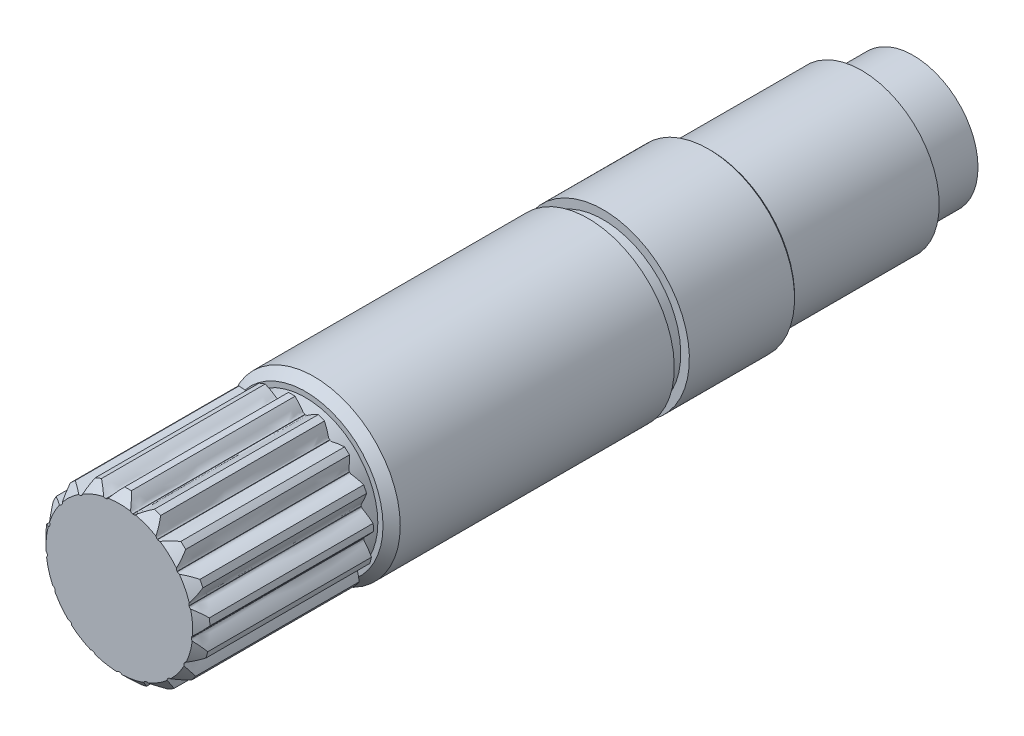
SolidWorks part; units mm, degrees
material "Alloy Steel"
ref_plane "Front Plane" through (0, 0, 0) normal (0, 0, 1) x (1, 0, 0)
ref_plane "Top Plane" through (0, 0, 0) normal (0, 1, 0) x (1, 0, 0)
ref_plane "Right Plane" through (0, 0, 0) normal (1, 0, 0) x (0, 0, -1)
sketch "Sketch12" plane through (0, 0, 0) normal (0, 0, 1) x (1, 0, 0)
  circle A0 centre (0, 0) radius 10
  dimension "D1" = 20
extrude "Shaft" add sketch "Sketch12" along normal mid plane 43
sketch "Sketch13" plane through (0, 0, 21.5) normal (0, 0, 1) x (1, 0, 0)
  circle A0 centre (0, 0) radius 8.3981
  dimension "D1" = 16.7963
extrude "Motor side relief" add sketch "Sketch13" along normal blind 1.587
sketch "Sketch14" plane through (0, 0, -21.5) normal (0, 0, -1) x (-1, 0, 0)
  circle A0 centre (0, 0) radius 8.3981
  dimension "D1" = 16.7963
sketch "Sketch15" plane through (0, 0, 23.087) normal (0, 0, 1) x (1, 0, 0)
  line L38 (4.4402, 7.1283) -> (4.4211, 7.1402)
  line L39 (4.4211, 7.1402) -> (4.4019, 7.1521)
  line L40 (1.5653, 8.251) -> (1.5432, 8.2552)
  line L41 (1.5432, 8.2552) -> (1.521, 8.2593)
  line L42 (-1.521, 8.2593) -> (-1.5432, 8.2552)
  line L43 (-1.5432, 8.2552) -> (-1.5653, 8.251)
  line L44 (-4.4019, 7.1521) -> (-4.4211, 7.1402)
  line L45 (-4.4211, 7.1402) -> (-4.4402, 7.1283)
  line L46 (-6.6882, 5.079) -> (-6.7019, 5.061)
  line L47 (-6.7019, 5.061) -> (-6.7154, 5.043)
  line L48 (-8.0713, 2.32) -> (-8.0776, 2.2983)
  line L49 (-8.0776, 2.2983) -> (-8.0837, 2.2766)
  line L50 (-8.3644, -0.7524) -> (-8.3623, -0.7749)
  line L51 (-8.3623, -0.7749) -> (-8.3602, -0.7973)
  line L52 (-7.5277, -3.7232) -> (-7.5177, -3.7434)
  line L53 (-7.5177, -3.7434) -> (-7.5076, -3.7636)
  line L54 (-5.6744, -6.1911) -> (-5.6578, -6.2063)
  line L55 (-5.6578, -6.2063) -> (-5.6411, -6.2215)
  line L56 (-3.0548, -7.8229) -> (-3.0338, -7.831)
  line L57 (-3.0338, -7.831) -> (-3.0127, -7.8392)
  line L58 (-0.0226, -8.3981) -> (0, -8.3981)
  line L59 (0, -8.3981) -> (0.0226, -8.3981)
  line L60 (3.0127, -7.8392) -> (3.0338, -7.831)
  line L61 (3.0338, -7.831) -> (3.0548, -7.8229)
  line L62 (5.6411, -6.2215) -> (5.6578, -6.2063)
  line L63 (5.6578, -6.2063) -> (5.6744, -6.1911)
  line L64 (7.5076, -3.7636) -> (7.5177, -3.7434)
  line L65 (7.5177, -3.7434) -> (7.5277, -3.7232)
  line L66 (8.3602, -0.7973) -> (8.3623, -0.7749)
  line L67 (8.3623, -0.7749) -> (8.3644, -0.7524)
  line L68 (8.0837, 2.2766) -> (8.0776, 2.2983)
  line L69 (8.0776, 2.2983) -> (8.0713, 2.32)
  line L70 (6.7154, 5.043) -> (6.7019, 5.061)
  line L71 (6.7019, 5.061) -> (6.6882, 5.079)
  arc A19 (6.6912, 6.7683) -> (6.1221, 7.2872) centre (0, 0) ccw
  arc A20 (3.7944, 8.7284) -> (3.0762, 9.0066) centre (0, 0) ccw
  arc A21 (0.3851, 9.5097) -> (-0.3851, 9.5097) centre (0, 0) ccw
  arc A22 (-3.0762, 9.0066) -> (-3.7944, 8.7284) centre (0, 0) ccw
  arc A23 (-6.1221, 7.2872) -> (-6.6912, 6.7683) centre (0, 0) ccw
  arc A24 (-8.3411, 4.5835) -> (-8.6844, 3.8941) centre (0, 0) ccw
  arc A25 (-9.4336, 1.2609) -> (-9.5047, 0.494) centre (0, 0) ccw
  arc A26 (-9.2521, -2.2321) -> (-9.0413, -2.9728) centre (0, 0) ccw
  arc A27 (-7.821, -5.4236) -> (-7.3569, -6.0382) centre (0, 0) ccw
  arc A28 (-5.3336, -7.8826) -> (-4.6788, -8.288) centre (0, 0) ccw
  arc A29 (-2.1259, -9.277) -> (-1.3689, -9.4185) centre (0, 0) ccw
  arc A30 (1.3689, -9.4185) -> (2.1259, -9.277) centre (0, 0) ccw
  arc A31 (4.6788, -8.288) -> (5.3336, -7.8826) centre (0, 0) ccw
  arc A32 (7.3569, -6.0382) -> (7.821, -5.4236) centre (0, 0) ccw
  arc A33 (9.0413, -2.9728) -> (9.2521, -2.2321) centre (0, 0) ccw
  arc A34 (9.5047, 0.494) -> (9.4336, 1.2609) centre (0, 0) ccw
  arc A35 (8.6844, 3.8941) -> (8.3411, 4.5835) centre (0, 0) ccw
  spline S0 degree 3 poles (6.6882, 5.079) (6.6486, 5.1312) (6.6257, 5.1903) (6.6128, 5.3124) (6.6277, 5.3769) (6.657, 5.5736) (6.6884, 5.8472) (6.7084, 6.2901) (6.7009, 6.6058) (6.6912, 6.7683) knots 0 0 0 0 0.125 0.125 0.25 0.25 0.5 0.75 1 1 1 1 weights 1 1 1 1 1 1 1 1 1 1
  spline S1 degree 3 poles (6.1221, 7.2872) (5.9593, 7.2818) (5.6443, 7.2602) (5.2052, 7.1994) (4.9356, 7.1428) (4.7425, 7.0956) (4.6796, 7.0748) (4.5569, 7.0763) (4.4958, 7.0937) (4.4402, 7.1283) knots 0 0 0 0 0.25 0.5 0.75 0.75 0.875 0.875 1 1 1 1 weights 1 1 1 1 1 1 1 1 1 1
  spline S2 degree 3 poles (4.4019, 7.1521) (4.3461, 7.1864) (4.3033, 7.2333) (4.2472, 7.3425) (4.2378, 7.4081) (4.194, 7.602) (4.1245, 7.8685) (3.9832, 8.2887) (3.8621, 8.5804) (3.7944, 8.7284) knots 0 0 0 0 0.125 0.125 0.25 0.25 0.5 0.75 1 1 1 1 weights 1 1 1 1 1 1 1 1 1 1
  spline S3 degree 3 poles (3.0762, 9.0066) (2.9264, 8.9428) (2.6405, 8.8089) (2.253, 8.5935) (2.022, 8.4434) (1.859, 8.3296) (1.8079, 8.2875) (1.6929, 8.2446) (1.6297, 8.2388) (1.5653, 8.251) knots 0 0 0 0 0.25 0.5 0.75 0.75 0.875 0.875 1 1 1 1 weights 1 1 1 1 1 1 1 1 1 1
  spline S4 degree 3 poles (1.521, 8.2593) (1.4566, 8.2711) (1.3997, 8.2994) (1.308, 8.3809) (1.2755, 8.4387) (1.1646, 8.6037) (1.0035, 8.8271) (0.7199, 9.1679) (0.5017, 9.3961) (0.3851, 9.5097) knots 0 0 0 0 0.125 0.125 0.25 0.25 0.5 0.75 1 1 1 1 weights 1 1 1 1 1 1 1 1 1 1
  spline S5 degree 3 poles (-0.3851, 9.5097) (-0.5017, 9.3961) (-0.7199, 9.1679) (-1.0035, 8.8271) (-1.1646, 8.6037) (-1.2755, 8.4387) (-1.308, 8.3809) (-1.3997, 8.2994) (-1.4566, 8.2711) (-1.521, 8.2593) knots 0 0 0 0 0.25 0.5 0.75 0.75 0.875 0.875 1 1 1 1 weights 1 1 1 1 1 1 1 1 1 1
  spline S6 degree 3 poles (-1.5653, 8.251) (-1.6297, 8.2388) (-1.6929, 8.2446) (-1.8079, 8.2875) (-1.859, 8.3296) (-2.022, 8.4434) (-2.253, 8.5935) (-2.6405, 8.8089) (-2.9264, 8.9428) (-3.0762, 9.0066) knots 0 0 0 0 0.125 0.125 0.25 0.25 0.5 0.75 1 1 1 1 weights 1 1 1 1 1 1 1 1 1 1
  spline S7 degree 3 poles (-3.7944, 8.7284) (-3.8621, 8.5804) (-3.9832, 8.2887) (-4.1245, 7.8685) (-4.194, 7.602) (-4.2378, 7.4081) (-4.2472, 7.3425) (-4.3033, 7.2333) (-4.3461, 7.1864) (-4.4019, 7.1521) knots 0 0 0 0 0.25 0.5 0.75 0.75 0.875 0.875 1 1 1 1 weights 1 1 1 1 1 1 1 1 1 1
  spline S8 degree 3 poles (-4.4402, 7.1283) (-4.4958, 7.0937) (-4.5569, 7.0763) (-4.6796, 7.0748) (-4.7425, 7.0956) (-4.9356, 7.1428) (-5.2052, 7.1994) (-5.6443, 7.2602) (-5.9593, 7.2818) (-6.1221, 7.2872) knots 0 0 0 0 0.125 0.125 0.25 0.25 0.5 0.75 1 1 1 1 weights 1 1 1 1 1 1 1 1 1 1
  spline S9 degree 3 poles (-6.6912, 6.7683) (-6.7009, 6.6058) (-6.7084, 6.2901) (-6.6884, 5.8472) (-6.657, 5.5736) (-6.6277, 5.3769) (-6.6128, 5.3124) (-6.6257, 5.1903) (-6.6486, 5.1312) (-6.6882, 5.079) knots 0 0 0 0 0.25 0.5 0.75 0.75 0.875 0.875 1 1 1 1 weights 1 1 1 1 1 1 1 1 1 1
  spline S10 degree 3 poles (-6.7154, 5.043) (-6.7548, 4.9906) (-6.8054, 4.9523) (-6.9193, 4.9066) (-6.9854, 4.9033) (-7.1826, 4.8775) (-7.4544, 4.8329) (-7.8859, 4.7309) (-8.1874, 4.6373) (-8.3411, 4.5835) knots 0 0 0 0 0.125 0.125 0.25 0.25 0.5 0.75 1 1 1 1 weights 1 1 1 1 1 1 1 1 1 1
  spline S11 degree 3 poles (-8.6844, 3.8941) (-8.6347, 3.7391) (-8.5277, 3.442) (-8.349, 3.0363) (-8.2209, 2.7925) (-8.1225, 2.6196) (-8.0853, 2.5648) (-8.0532, 2.4464) (-8.0533, 2.3829) (-8.0713, 2.32) knots 0 0 0 0 0.25 0.5 0.75 0.75 0.875 0.875 1 1 1 1 weights 1 1 1 1 1 1 1 1 1 1
  spline S12 degree 3 poles (-8.0837, 2.2766) (-8.1015, 2.2135) (-8.1348, 2.1595) (-8.2245, 2.0757) (-8.285, 2.0487) (-8.4596, 1.9535) (-8.6968, 1.8137) (-9.0624, 1.5628) (-9.3097, 1.3665) (-9.4336, 1.2609) knots 0 0 0 0 0.125 0.125 0.25 0.25 0.5 0.75 1 1 1 1 weights 1 1 1 1 1 1 1 1 1 1
  spline S13 degree 3 poles (-9.5047, 0.494) (-9.4023, 0.3674) (-9.1952, 0.129) (-8.882, -0.1848) (-8.6745, -0.3658) (-8.5204, -0.4915) (-8.4659, -0.5291) (-8.3931, -0.628) (-8.3702, -0.6872) (-8.3644, -0.7524) knots 0 0 0 0 0.25 0.5 0.75 0.75 0.875 0.875 1 1 1 1 weights 1 1 1 1 1 1 1 1 1 1
  spline S14 degree 3 poles (-8.3602, -0.7973) (-8.354, -0.8625) (-8.3656, -0.925) (-8.419, -1.0355) (-8.4656, -1.0825) (-8.594, -1.2344) (-8.7647, -1.4504) (-9.0149, -1.8164) (-9.1747, -2.0888) (-9.2521, -2.2321) knots 0 0 0 0 0.125 0.125 0.25 0.25 0.5 0.75 1 1 1 1 weights 1 1 1 1 1 1 1 1 1 1
  spline S15 degree 3 poles (-9.0413, -2.9728) (-8.9001, -3.0539) (-8.6209, -3.2014) (-8.2155, -3.3809) (-7.9566, -3.4747) (-7.7675, -3.5362) (-7.7031, -3.5516) (-7.5995, -3.6175) (-7.5568, -3.6645) (-7.5277, -3.7232) knots 0 0 0 0 0.25 0.5 0.75 0.75 0.875 0.875 1 1 1 1 weights 1 1 1 1 1 1 1 1 1 1
  spline S16 degree 3 poles (-7.5076, -3.7636) (-7.4783, -3.8221) (-7.4666, -3.8845) (-7.4764, -4.0068) (-7.5029, -4.0675) (-7.5678, -4.2555) (-7.6489, -4.5187) (-7.75, -4.9504) (-7.8006, -5.262) (-7.821, -5.4236) knots 0 0 0 0 0.125 0.125 0.25 0.25 0.5 0.75 1 1 1 1 weights 1 1 1 1 1 1 1 1 1 1
  spline S17 degree 3 poles (-7.3569, -6.0382) (-7.1959, -6.0628) (-6.8823, -6.0994) (-6.4394, -6.1203) (-6.1641, -6.1143) (-5.9655, -6.1033) (-5.8999, -6.0945) (-5.7795, -6.1185) (-5.7227, -6.1468) (-5.6744, -6.1911) knots 0 0 0 0 0.25 0.5 0.75 0.75 0.875 0.875 1 1 1 1 weights 1 1 1 1 1 1 1 1 1 1
  spline S18 degree 3 poles (-5.6411, -6.2215) (-5.5926, -6.2655) (-5.5591, -6.3194) (-5.5241, -6.437) (-5.5269, -6.5032) (-5.5195, -6.7019) (-5.5001, -6.9766) (-5.4384, -7.4157) (-5.373, -7.7246) (-5.3336, -7.8826) knots 0 0 0 0 0.125 0.125 0.25 0.25 0.5 0.75 1 1 1 1 weights 1 1 1 1 1 1 1 1 1 1
  spline S19 degree 3 poles (-4.6788, -8.288) (-4.5198, -8.2528) (-4.2142, -8.1737) (-3.7936, -8.0332) (-3.5391, -7.9281) (-3.3579, -7.8462) (-3.2999, -7.8142) (-3.179, -7.7931) (-3.1158, -7.799) (-3.0548, -7.8229) knots 0 0 0 0 0.25 0.5 0.75 0.75 0.875 0.875 1 1 1 1 weights 1 1 1 1 1 1 1 1 1 1
  spline S20 degree 3 poles (-3.0127, -7.8392) (-2.9516, -7.8627) (-2.9009, -7.9009) (-2.8257, -7.9979) (-2.8044, -8.0606) (-2.7257, -8.2432) (-2.6084, -8.4924) (-2.3923, -8.8795) (-2.2197, -9.1439) (-2.1259, -9.277) knots 0 0 0 0 0.125 0.125 0.25 0.25 0.5 0.75 1 1 1 1 weights 1 1 1 1 1 1 1 1 1 1
  spline S21 degree 3 poles (-1.3689, -9.4185) (-1.2333, -9.3283) (-0.9769, -9.1441) (-0.6355, -8.8612) (-0.4361, -8.6712) (-0.2968, -8.5294) (-0.2543, -8.4786) (-0.1491, -8.4153) (-0.0881, -8.3979) (-0.0226, -8.3981) knots 0 0 0 0 0.25 0.5 0.75 0.75 0.875 0.875 1 1 1 1 weights 1 1 1 1 1 1 1 1 1 1
  spline S22 degree 3 poles (0.0226, -8.3981) (0.0881, -8.3979) (0.1491, -8.4153) (0.2543, -8.4786) (0.2968, -8.5294) (0.4361, -8.6712) (0.6355, -8.8612) (0.9769, -9.1441) (1.2333, -9.3283) (1.3689, -9.4185) knots 0 0 0 0 0.125 0.125 0.25 0.25 0.5 0.75 1 1 1 1 weights 1 1 1 1 1 1 1 1 1 1
  spline S23 degree 3 poles (2.1259, -9.277) (2.2197, -9.1439) (2.3923, -8.8795) (2.6084, -8.4924) (2.7257, -8.2432) (2.8044, -8.0606) (2.8257, -7.9979) (2.9009, -7.9009) (2.9516, -7.8627) (3.0127, -7.8392) knots 0 0 0 0 0.25 0.5 0.75 0.75 0.875 0.875 1 1 1 1 weights 1 1 1 1 1 1 1 1 1 1
  spline S24 degree 3 poles (3.0548, -7.8229) (3.1158, -7.799) (3.179, -7.7931) (3.2999, -7.8142) (3.3579, -7.8462) (3.5391, -7.9281) (3.7936, -8.0332) (4.2142, -8.1737) (4.5198, -8.2528) (4.6788, -8.288) knots 0 0 0 0 0.125 0.125 0.25 0.25 0.5 0.75 1 1 1 1 weights 1 1 1 1 1 1 1 1 1 1
  spline S25 degree 3 poles (5.3336, -7.8826) (5.373, -7.7246) (5.4384, -7.4157) (5.5001, -6.9766) (5.5195, -6.7019) (5.5269, -6.5032) (5.5241, -6.437) (5.5591, -6.3194) (5.5926, -6.2655) (5.6411, -6.2215) knots 0 0 0 0 0.25 0.5 0.75 0.75 0.875 0.875 1 1 1 1 weights 1 1 1 1 1 1 1 1 1 1
  spline S26 degree 3 poles (5.6744, -6.1911) (5.7227, -6.1468) (5.7795, -6.1185) (5.8999, -6.0945) (5.9655, -6.1033) (6.1641, -6.1143) (6.4394, -6.1203) (6.8823, -6.0994) (7.1959, -6.0628) (7.3569, -6.0382) knots 0 0 0 0 0.125 0.125 0.25 0.25 0.5 0.75 1 1 1 1 weights 1 1 1 1 1 1 1 1 1 1
  spline S27 degree 3 poles (7.821, -5.4236) (7.8006, -5.262) (7.75, -4.9504) (7.6489, -4.5187) (7.5678, -4.2555) (7.5029, -4.0675) (7.4764, -4.0068) (7.4666, -3.8845) (7.4783, -3.8221) (7.5076, -3.7636) knots 0 0 0 0 0.25 0.5 0.75 0.75 0.875 0.875 1 1 1 1 weights 1 1 1 1 1 1 1 1 1 1
  spline S28 degree 3 poles (7.5277, -3.7232) (7.5568, -3.6645) (7.5995, -3.6175) (7.7031, -3.5516) (7.7675, -3.5362) (7.9566, -3.4747) (8.2155, -3.3809) (8.6209, -3.2014) (8.9001, -3.0539) (9.0413, -2.9728) knots 0 0 0 0 0.125 0.125 0.25 0.25 0.5 0.75 1 1 1 1 weights 1 1 1 1 1 1 1 1 1 1
  spline S29 degree 3 poles (9.2521, -2.2321) (9.1747, -2.0888) (9.0149, -1.8164) (8.7647, -1.4504) (8.594, -1.2344) (8.4656, -1.0825) (8.419, -1.0355) (8.3656, -0.925) (8.354, -0.8625) (8.3602, -0.7973) knots 0 0 0 0 0.25 0.5 0.75 0.75 0.875 0.875 1 1 1 1 weights 1 1 1 1 1 1 1 1 1 1
  spline S30 degree 3 poles (8.3644, -0.7524) (8.3702, -0.6872) (8.3931, -0.628) (8.4659, -0.5291) (8.5204, -0.4915) (8.6745, -0.3658) (8.882, -0.1848) (9.1952, 0.129) (9.4023, 0.3674) (9.5047, 0.494) knots 0 0 0 0 0.125 0.125 0.25 0.25 0.5 0.75 1 1 1 1 weights 1 1 1 1 1 1 1 1 1 1
  spline S31 degree 3 poles (9.4336, 1.2609) (9.3097, 1.3665) (9.0624, 1.5628) (8.6968, 1.8137) (8.4596, 1.9535) (8.285, 2.0487) (8.2245, 2.0757) (8.1348, 2.1595) (8.1015, 2.2135) (8.0837, 2.2766) knots 0 0 0 0 0.25 0.5 0.75 0.75 0.875 0.875 1 1 1 1 weights 1 1 1 1 1 1 1 1 1 1
  spline S32 degree 3 poles (8.0713, 2.32) (8.0533, 2.3829) (8.0532, 2.4464) (8.0853, 2.5648) (8.1225, 2.6196) (8.2209, 2.7925) (8.349, 3.0363) (8.5277, 3.442) (8.6347, 3.7391) (8.6844, 3.8941) knots 0 0 0 0 0.125 0.125 0.25 0.25 0.5 0.75 1 1 1 1 weights 1 1 1 1 1 1 1 1 1 1
  spline S33 degree 3 poles (8.3411, 4.5835) (8.1874, 4.6373) (7.8858, 4.731) (7.4544, 4.8329) (7.1826, 4.8775) (6.9854, 4.9033) (6.9193, 4.9066) (6.8054, 4.9523) (6.7548, 4.9906) (6.7154, 5.043) knots 0 0 0 0 0.25 0.5 0.75 0.75 0.875 0.875 1 1 1 1 weights 1 1 1 1 1 1 1 1 1 1
extrude "Motor spline" add sketch "Sketch15" along normal blind 20
chamfer "Chamfer3" distance 1 angle 45 1 edges at (10, 0, 21.5)
sketch "Sketch23" plane through (0, 0, -31.5) normal (-0.9982, 0.0593, 0) x (-0.0593, -0.9982, 0)
  line L0 (10, 20.2042) -> (9, 20.2042)
  line L1 (9, 20.2042) -> (9, 18.4542)
  line L2 (9, 18.4542) -> (10, 18.4542)
  line L3 (10, 18.4542) -> (10, 20.2042)
  line L4 (10, 10) -> (10, 52) construction
  line L5 (-13.85, 20.2042) -> (13.85, 20.2042) construction
  line L7 (0, 185.3358) -> (0, -121.609) construction
  dimension "D1" = 1.75
  dimension "D2" = 1
revolve "snap ring" cut sketch "Sketch23" angle 360 about L7
sketch "Sketch24" plane through (0, 0, 0) normal (0, 1, 0) x (1, 0, 0)
  line L3 (10, 21.5) -> (10, 25.5)
  line L5 (7.5, 43.5) -> (7.5, 49.5)
  line L6 (7.5, 49.5) -> (0, 49.5)
  line L7 (0, 49.5) -> (0, 21.5)
  line L8 (10, 21.5) -> (-10, 21.5) construction
  line L9 (0, 21.5) -> (10, 21.5)
  line L10 (0, 0) -> (0, 49.7252) construction
  line L12 (7.5, 43.5) -> (9, 43.5)
  line L14 (10, 25.5) -> (9, 25.5)
  line L15 (9, 25.5) -> (9, 43.5)
  dimension "D1" = 15
  dimension "D2" = 22
  dimension "D3" = 4
  dimension "D8" = 6
revolve "Revolve1" add sketch "Sketch24" angle 360 about L10
chamfer "Chamfer4" distance 1 angle 25 2 edges at (9, 0, -43.5) (7.5, 0, -49.5) first distance on face at (7.5, 0, -43.5) first distance on face at (7.5, 0, -49.5)
chamfer "Chamfer5" distance 0.25 angle 45 1 edges at (10, 0, -25.5)
chamfer "Chamfer6" distance 1 angle 45 17 edges
sketch "Sketch25" plane through (0, 0, 0) normal (0, 1, 0) x (1, 0, 0)
  line L0 (0, 0) -> (0, 56.6096) construction
  line L1 (-8.5, 37.5) -> (-8.5, 38.8)
  line L2 (9.75, 25.5) -> (-9.75, 25.5) construction
  line L3 (-8.5, 38.8) -> (-10.5, 38.8)
  line L4 (-10.5, 38.8) -> (-10.5, 37.5)
  line L5 (-10.5, 37.5) -> (-8.5, 37.5)
  dimension "D1" = 17
  dimension "D2" = 1.3
  dimension "D3" = 12
  dimension "D4" = 2
revolve "Cut-Revolve1" [suppressed] cut sketch "Sketch25" angle 360 about L0
